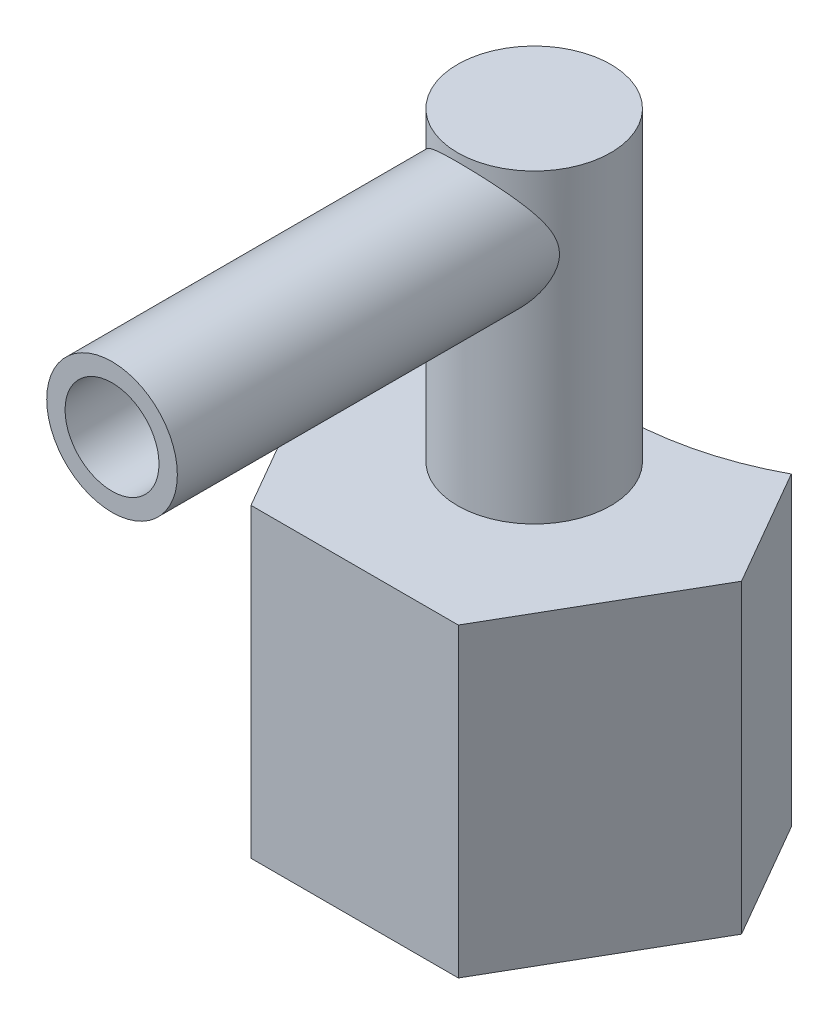
SolidWorks part; units mm, degrees
material "1060 Alloy"
ref_plane "Front Plane" through (0, 0, 0) normal (0, 0, 1) x (1, 0, 0)
ref_plane "Top Plane" through (0, 0, 0) normal (0, 1, 0) x (1, 0, 0)
ref_plane "Right Plane" through (0, 0, 0) normal (1, 0, 0) x (0, 0, -1)
sketch "Sketch1" plane through (0, 0, 0) normal (0, 1, 0) x (1, 0, 0)
  circle A0 centre (0, 0) radius 4.7625
  circle A1 centre (0, 0) radius 3.175
  dimension "D1" = 9.525
extrude "Boss-Extrude1" add sketch "Sketch1" along normal blind 8.3312
sketch "Sketch2" plane through (0, 8.3312, 0) normal (0, 1, 0) x (1, 0, 0)
  line L1 (5.6506, 0) -> (2.8253, 4.8936)
  line L2 (2.8253, 4.8936) -> (-2.8253, 4.8936)
  line L3 (-2.8253, 4.8936) -> (-5.6506, 0)
  line L4 (-5.6506, 0) -> (-2.8253, -4.8936)
  line L5 (-2.8253, -4.8936) -> (2.8253, -4.8936)
  line L6 (2.8253, -4.8936) -> (5.6506, 0)
  circle A0 centre (0, 0) radius 4.8936 construction
extrude "Boss-Extrude2" add sketch "Sketch2" along normal blind 8.3312
sketch "Sketch3" plane through (0, 16.6624, 0) normal (0, 1, 0) x (1, 0, 0)
  circle A0 centre (0, 0) radius 1.5875
  circle A1 centre (0, 0) radius 2.0875
  dimension "D1" = 3.175
  dimension "D2" = 0.5
extrude "Boss-Extrude3" add sketch "Sketch3" along normal blind 8.3312
sketch "Sketch4" plane through (0, 24.9936, 0) normal (0, 1, 0) x (1, 0, 0)
  circle A0 centre (0, 0) radius 2.0875
extrude "Boss-Extrude4" add sketch "Sketch4" along normal blind 0.001
ref_plane "Plane1" through (0, 0, 0) normal (0, 0, 1) x (1, 0, 0)
sketch "Sketch5" plane through (0, 0, 0) normal (0, 0, 1) x (1, 0, 0)
  line L0 (0, 24.9946) -> (0, 22.9946) construction
  line L1 (2.0875, 24.9946) -> (-2.0875, 24.9946) construction
  circle A0 centre (0, 22.9946) radius 1.78
  circle A1 centre (0, 22.9946) radius 1.28
  dimension "D1" = 2
  dimension "D2" = 0.5
extrude "Boss-Extrude5" add sketch "Sketch5" along normal blind 11.5062
sketch "Sketch6" plane through (0, 0, 0) normal (0, -1, 0) x (1, 0, 0)
  circle A0 centre (0, 0) radius 10.2581
extrude "Cut-Extrude1" cut sketch "Sketch6" against normal up to surface (8.3312 mm away) up to face at (0, 8.3312, 0)
sketch "Sketch8" plane through (0, 8.3312, 0) normal (0, -1, 0) x (1, 0, 0)
  circle A0 centre (0, -10.25) radius 8
  dimension "D1" = 16
  dimension "D2" = 10.25
extrude "Cut-Extrude2" cut sketch "Sketch8" against normal through all both and the other way through all
